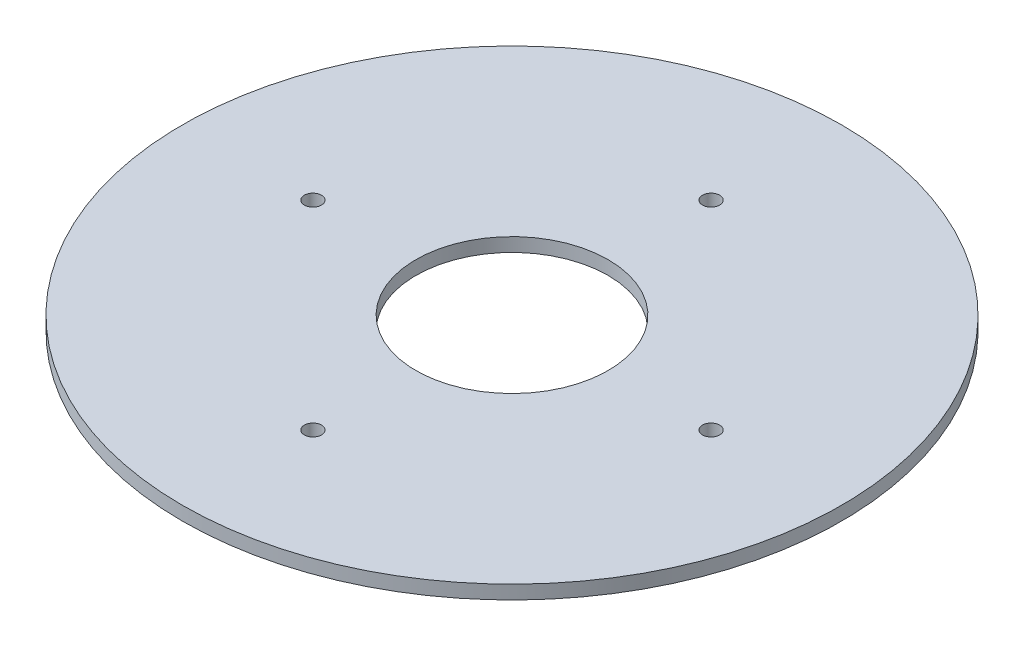
SolidWorks part; units mm, degrees
ref_plane "Front Plane" through (0, 0, 0) normal (0, 0, 1) x (1, 0, 0)
ref_plane "Top Plane" through (0, 0, 0) normal (0, 1, 0) x (1, 0, 0)
ref_plane "Right Plane" through (0, 0, 0) normal (1, 0, 0) x (0, 0, -1)
sketch "Sketch1" plane through (0, 0, 0) normal (0, 1, 0) x (1, 0, 0)
  line L0 (-46.0328, 0) -> (0, 46.0328) construction
  line L11 (0, 46.0328) -> (46.0328, 0) construction
  line L12 (46.0328, 0) -> (0, -46.0328) construction
  line L13 (0, -46.0328) -> (-46.0328, 0) construction
  line L14 (0, -46.0328) -> (0, 46.0328) construction
  line L15 (46.0328, 0) -> (-46.0328, 0) construction
  circle A0 centre (0, 0) radius 76.2
  circle A5 centre (0, 46.0328) radius 1.9844
  circle A6 centre (46.0328, 0) radius 1.9844
  circle A7 centre (0, -46.0328) radius 1.9844
  circle A8 centre (-46.0328, 0) radius 1.9844
  dimension "D1" = 152.4
extrude "Boss-Extrude1" add sketch "Sketch1" along normal blind 3.175
sketch "Sketch2" plane through (0, 0, 0) normal (0, -1, 0) x (1, 0, 0)
  circle A0 centre (0, 0) radius 22.225
  dimension "D1" = 44.45
extrude "Cut-Extrude1" cut sketch "Sketch2" against normal through all
